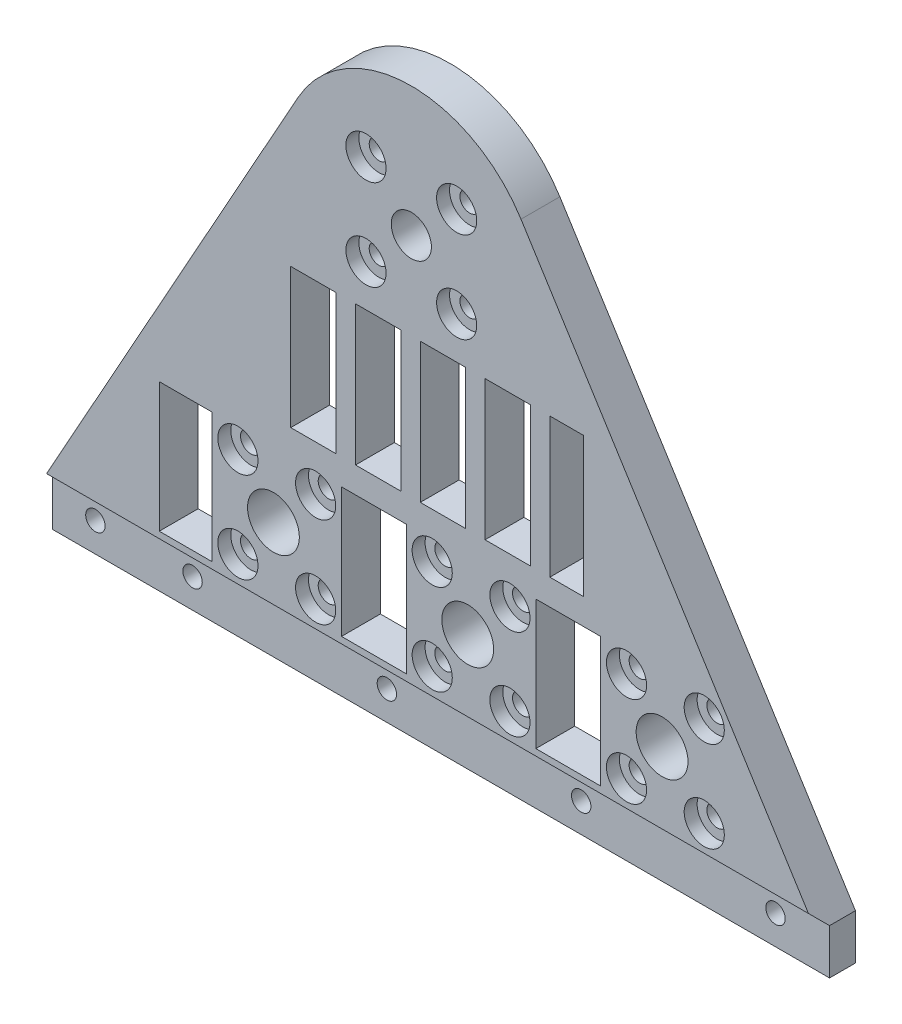
SolidWorks part; units mm, degrees
ref_plane "前视基准面" through (0, 0, 0) normal (0, 0, 1) x (1, 0, 0)
ref_plane "上视基准面" through (0, 0, 0) normal (0, 1, 0) x (1, 0, 0)
ref_plane "右视基准面" through (0, 0, 0) normal (1, 0, 0) x (0, 0, -1)
other "Configuration Table"
sketch "草图1" plane through (0, 0, 0) normal (0, 0, 1) x (1, 0, 0)
  line L5 (53.2118, 15.1053) -> (98.8463, -57.534)
  line L6 (18.8044, 14.1987) -> (-21.1537, -57.534)
  line L9 (98.8463, -57.534) -> (98.8463, -62.534)
  line L10 (98.8463, -62.534) -> (-21.1537, -62.534)
  line L11 (-21.1537, -62.534) -> (-21.1537, -57.534)
  arc A0 (53.2118, 15.1053) -> (18.8044, 14.1987) centre (36.2765, 4.466) ccw
  circle A2 centre (36.2765, 4.466) radius 3.1
  point P0 (0, 0)
extrude "凸台-拉伸1" add sketch "草图1" along normal blind 6
sketch "草图2" plane through (0, 0, 6) normal (0, 0, 1) x (1, 0, 0)
  line L0 (36.2765, 4.466) -> (36.2765, 16.549) construction
  line L5 (36.2765, 4.466) -> (44.4343, 4.466) construction
  circle A2 centre (29.2765, 11.466) radius 3.1
  circle A3 centre (43.2765, 11.466) radius 3.1
  circle A4 centre (43.2765, -2.534) radius 3.1
  circle A5 centre (29.2765, -2.534) radius 3.1
extrude "切除-拉伸6" cut sketch "草图2" against normal blind 2
sketch "草图4" plane through (0, 0, 4) normal (0, 0, 1) x (1, 0, 0)
  circle A0 centre (43.2765, 11.466) radius 1.5 construction
  circle A1 centre (43.2765, 11.466) radius 1.5
  circle A2 centre (43.2765, -2.534) radius 1.5 construction
  circle A3 centre (43.2765, -2.534) radius 1.5
  circle A4 centre (29.2765, -2.534) radius 1.5 construction
  circle A5 centre (29.2765, -2.534) radius 1.5
  circle A6 centre (29.2765, 11.466) radius 1.5 construction
  circle A7 centre (29.2765, 11.466) radius 1.5
extrude "切除-拉伸7" cut sketch "草图4" against normal through all
sketch "草图5" plane through (0, 0, 6) normal (0, 0, 1) x (1, 0, 0)
  line L0 (24.6608, -8.9774) -> (24.6608, -30.534)
  line L1 (14.6608, -8.9774) -> (62.8566, -8.9774)
  line L2 (14.6608, -8.9774) -> (14.6608, -30.534)
  line L3 (14.6608, -30.534) -> (62.8566, -30.534)
  line L4 (62.8566, -8.9774) -> (62.8566, -30.534)
  line L5 (14.6608, -8.9774) -> (17.6608, -8.9774)
  line L6 (14.6608, -8.9774) -> (14.6608, -30.534)
  line L7 (14.6608, -30.534) -> (17.6608, -30.534)
  line L8 (17.6608, -8.9774) -> (17.6608, -30.534)
  line L9 (24.6608, -8.9774) -> (27.6608, -8.9774)
  line L10 (27.6608, -8.9774) -> (27.6608, -30.534)
  line L11 (24.6608, -30.534) -> (27.6608, -30.534)
  line L12 (34.6608, -8.9774) -> (34.6608, -30.534)
  line L13 (34.6608, -8.9774) -> (37.6608, -8.9774)
  line L14 (37.6608, -8.9774) -> (37.6608, -30.534)
  line L15 (34.6608, -30.534) -> (37.6608, -30.534)
  line L16 (44.6608, -8.9774) -> (44.6608, -30.534)
  line L17 (44.6608, -8.9774) -> (47.6608, -8.9774)
  line L18 (47.6608, -8.9774) -> (47.6608, -30.534)
  line L19 (44.6608, -30.534) -> (47.6608, -30.534)
  line L20 (54.6608, -8.9774) -> (54.6608, -30.534)
  line L21 (54.6608, -8.9774) -> (57.6608, -8.9774)
  line L22 (57.6608, -8.9774) -> (57.6608, -30.534)
  line L23 (54.6608, -30.534) -> (57.6608, -30.534)
  line L24 (25.5023, -57.534) -> (25.5023, -31.534) construction
  line L25 (25.5023, -34.534) -> (35.5023, -34.534)
  line L26 (25.5023, -34.534) -> (25.5023, -54.534)
  line L27 (25.5023, -54.534) -> (35.5023, -54.534)
  line L28 (35.5023, -34.534) -> (35.5023, -54.534)
  line L29 (5.5023, -34.534) -> (115.5023, -34.534) construction
  line L30 (35.5023, -31.534) -> (35.5023, -57.534) construction
  line L31 (5.5023, -54.534) -> (115.5023, -54.534) construction
  line L32 (65.5023, -31.534) -> (65.5023, -57.534) construction
  line L33 (55.5023, -34.534) -> (65.5023, -34.534)
  line L34 (55.5023, -34.534) -> (55.5023, -54.534)
  line L35 (55.5023, -54.534) -> (65.5023, -54.534)
  line L36 (65.5023, -34.534) -> (65.5023, -54.534)
  line L38 (5.5023, -34.534) -> (-2.6351, -34.534)
  line L39 (5.5023, -34.534) -> (5.5023, -54.534)
  line L40 (5.5023, -54.534) -> (-2.6351, -54.534)
  line L41 (-2.6351, -34.534) -> (-2.6351, -54.534)
  circle A1 centre (14.9882, -44.534) radius 4 construction
  circle A2 centre (14.9882, -44.534) radius 4
  circle A3 centre (44.9882, -44.534) radius 4 construction
  circle A4 centre (44.9882, -44.534) radius 4
  circle A5 centre (74.9882, -44.534) radius 4 construction
  circle A6 centre (74.9882, -44.534) radius 4
  dimension "D1" = 3
  dimension "D3" = 5.1958
  dimension "D2" = 5
extrude "切除-拉伸8" cut sketch "草图5" against normal up to next contours L1 L8 L3 L0 | L12 L1 L10 L3 | L16 L1 L14 L3 | L20 L1 L18 L3 | L1 L22 L3 L4 | A2 | A4 | A6 | L38 L41 L40 L39 | L28 L25 L26 L27 | L36 L33 L34 L35 region at (21.1608, -19.7557, 6) region at (31.1608, -19.7557, 6) region at (41.1608, -19.7557, 6) region at (51.1608, -19.7557, 6) region at (60.2587, -19.7557, 6) region at (30.5023, -44.534, 6) region at (60.5023, -44.534, 6) region at (1.4336, -44.534, 6) region at (14.9882, -44.534, 6) region at (44.9882, -44.534, 6) region at (74.9882, -44.534, 6)
sketch "草图6" plane through (0, 0, 6) normal (0, 0, 1) x (1, 0, 0)
  circle A0 centre (21.5023, -37.534) radius 3.1
  circle A1 centre (9.5023, -37.534) radius 3.1
  circle A2 centre (9.5023, -51.534) radius 3.1
  circle A3 centre (21.5023, -51.534) radius 3.1
  circle A4 centre (39.5023, -37.534) radius 3.1
  circle A5 centre (51.5023, -37.534) radius 3.1
  circle A6 centre (51.5023, -51.534) radius 3.1
  circle A7 centre (39.5023, -51.534) radius 3.1
  circle A8 centre (69.5023, -37.534) radius 3.1
  circle A9 centre (81.5023, -37.534) radius 3.1
  circle A10 centre (81.5023, -51.534) radius 3.1
  circle A11 centre (69.5023, -51.534) radius 3.1
  dimension "D1" = 3
extrude "切除-拉伸9" cut sketch "草图6" against normal blind 2
sketch "草图7" plane through (0, 0, 4) normal (0, 0, 1) x (1, 0, 0)
  circle A0 centre (9.5023, -37.534) radius 1.6
  circle A1 centre (21.5023, -37.534) radius 1.6
  circle A2 centre (9.5023, -51.534) radius 1.6
  circle A3 centre (21.5023, -51.534) radius 1.6
  circle A4 centre (51.5023, -51.534) radius 1.6
  circle A5 centre (39.5023, -51.534) radius 1.6
  circle A6 centre (39.5023, -37.534) radius 1.6
  circle A7 centre (51.5023, -37.534) radius 1.6
  circle A8 centre (81.5023, -51.534) radius 1.6
  circle A9 centre (69.5023, -51.534) radius 1.6
  circle A10 centre (69.5023, -37.534) radius 1.6
  circle A11 centre (81.5023, -37.534) radius 1.6
  dimension "D1" = 3
  dimension "D2" = 3.2
  dimension "D3" = 3.2
  dimension "D4" = 3.2
  dimension "D5" = 3.2
extrude "切除-拉伸10" cut sketch "草图7" against normal through all
sketch "草图8" plane through (0, 0, 6) normal (0, 0, 1) x (1, 0, 0)
  circle A0 centre (90.5023, -60.034) radius 1.5 construction
  circle A1 centre (90.5023, -60.034) radius 1.5
  circle A2 centre (60.5023, -60.034) radius 1.5 construction
  circle A3 centre (60.5023, -60.034) radius 1.5
  circle A4 centre (30.5023, -60.034) radius 1.5 construction
  circle A5 centre (30.5023, -60.034) radius 1.5
  circle A6 centre (0.5023, -60.034) radius 1.5 construction
  circle A7 centre (0.5023, -60.034) radius 1.5
  circle A8 centre (-14.4977, -60.034) radius 1.5 construction
  circle A9 centre (-14.4977, -60.034) radius 1.5
extrude "切除-拉伸11" cut sketch "草图8" against normal through all
sketch "草图9" plane through (0, 0, 6) normal (0, 0, 1) x (1, 0, 0)
  line L4 (-21.1537, -62.534) -> (98.8463, -62.534)
  line L5 (98.8463, -62.534) -> (98.8463, -57.534)
  line L6 (98.8463, -57.534) -> (-21.1537, -57.534)
  line L7 (-21.1537, -57.534) -> (-21.1537, -62.534)
  line L8 (-21.1537, -62.534) -> (98.8463, -62.534)
  line L9 (98.8463, -62.534) -> (98.8463, -57.534)
  line L10 (98.8463, -57.534) -> (-21.1537, -57.534)
  line L11 (-21.1537, -57.534) -> (-21.1537, -62.534)
  dimension "D1" = 0
extrude "切除-拉伸12" cut sketch "草图9" against normal blind 2
chamfer "倒角1" distance 2 angle 45 1 edges at (38.8463, -57.534, 6)
sketch "草图10" plane through (0, -62.534, 0) normal (0, -1, 0) x (1, 0, 0)
  line L4 (98.8463, 4) -> (-21.1537, 4)
  line L5 (-21.1537, 4) -> (-21.1537, 0)
  line L6 (-21.1537, 0) -> (98.8463, 0)
  line L7 (98.8463, 0) -> (98.8463, 4)
  line L8 (98.8463, 4) -> (-21.1537, 4)
  line L9 (-21.1537, 4) -> (-21.1537, 0)
  line L10 (-21.1537, 0) -> (98.8463, 0)
  line L11 (98.8463, 0) -> (98.8463, 4)
  dimension "D1" = 0
extrude "凸台-拉伸2" add sketch "草图10" along normal blind 2
